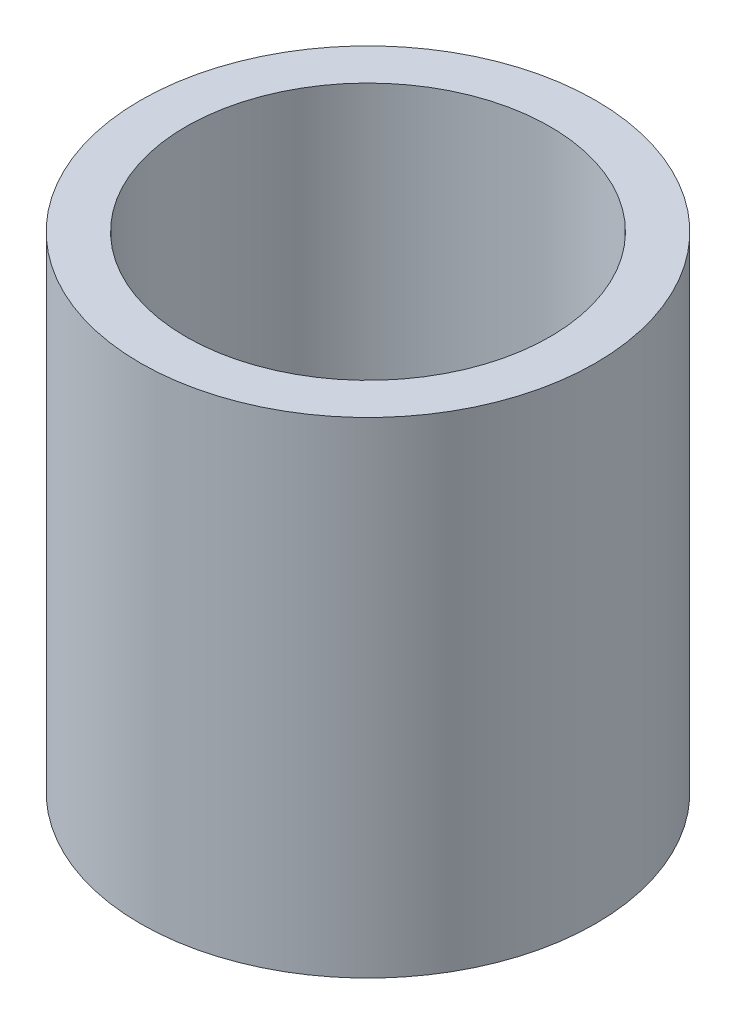
SolidWorks part; units mm, degrees
ref_plane "Front Plane" through (0, 0, 0) normal (0, 0, 1) x (1, 0, 0)
ref_plane "Top Plane" through (0, 0, 0) normal (0, 1, 0) x (1, 0, 0)
ref_plane "Right Plane" through (0, 0, 0) normal (1, 0, 0) x (0, 0, -1)
sketch "Sketch1" plane through (0, 0, 0) normal (0, 1, 0) x (1, 0, 0)
  circle A0 centre (0, 0) radius 3.3
  circle A1 centre (0, 0) radius 15
  circle A2 centre (0, 0) radius 12
  dimension "D1" = 6.6
  dimension "D2" = 30
  dimension "D3" = 24
extrude "Boss-Extrude1" add sketch "Sketch1" along normal blind 2 contours A1 A2 | A2 A0 region at (-14.5757, 0, 0) region at (-11.6606, 0, 0)
extrude "Boss-Extrude2" add sketch "Sketch1<3>" along normal blind 32 contours A1 A2 region at (-14.5757, 0, 0)
sketch "Sketch1<3>" plane through (0, 0, 0) normal (0, 1, 0) x (1, 0, 0) same geometry as "Sketch1"
ref_plane "Plane1" through (13, 0, 0) normal (1, 0, 0) x (0, 0, -1)
sketch "Sketch3" plane through (13, 0, 0) normal (1, 0, 0) x (0, 0, -1)
  line L1 (0, 26.4135) -> (0, 47.2406) construction
  line L2 (15, 32) -> (-15, 32) construction
  line L3 (15, 32) -> (-15, 32)
  line L5 (-4, 32) -> (4, 32)
  line L6 (-4, 32) -> (-4, 31)
  line L7 (-4, 31) -> (4, 31)
  line L8 (4, 32) -> (4, 31)
  point P2 (0, 31)
  point P5 (0, 32)
  point P10 (0, 0)
  point P11 (0, 0)
  dimension "D1" = 8
  dimension "D2" = 1
